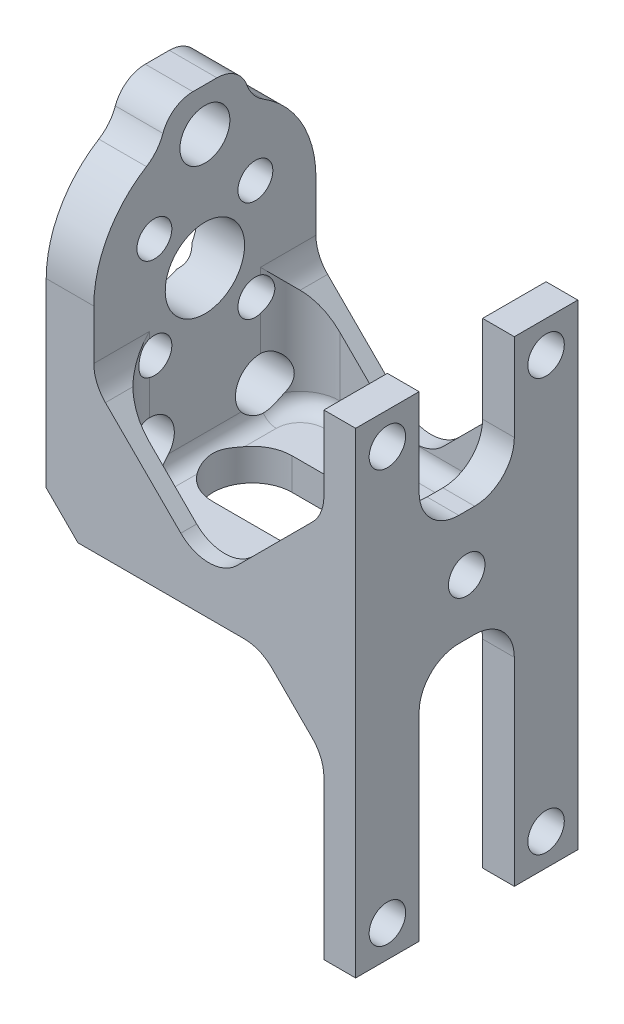
SolidWorks part; units mm, degrees
ref_plane "Front Plane" through (0, 0, 0) normal (0, 0, 1) x (1, 0, 0)
ref_plane "Top Plane" through (0, 0, 0) normal (0, 1, 0) x (1, 0, 0)
ref_plane "Right Plane" through (0, 0, 0) normal (1, 0, 0) x (0, 0, -1)
sketch "Sketch1" plane through (0, 0, 0) normal (0, 1, 0) x (1, 0, 0)
  line L0 (-7.25, 7) -> (7.25, -7) construction
  line L1 (-7.25, 7) -> (7.25, 7)
  line L2 (-7.25, 7) -> (-7.25, -7)
  line L3 (-7.25, -7) -> (7.25, -7)
  line L4 (7.25, 7) -> (7.25, -7)
  dimension "D2" = 14.5
  dimension "D1" = 14
extrude "base" add sketch "Sketch1" along normal blind 2
sketch "Sketch3" plane through (0, 0, 7) normal (0, 0, 1) x (1, 0, 0)
  line L0 (-7.25, 2) -> (7.25, 2) construction
  line L1 (-7.25, 0) -> (-10.25, 0)
  line L2 (-7.25, 0) -> (-7.25, 19)
  line L3 (-7.25, 19) -> (-10.25, 19)
  line L4 (-10.25, 0) -> (-10.25, 19)
  dimension "D1" = 3
  dimension "D2" = 17
extrude "motorFlange" add sketch "Sketch3" against normal up to surface (14 mm away) up to face at (0, 1, -7)
hole_wizard "CSK for M2 Flat Head Machine Screw1" positions "Sketch6" profile "Sketch7" countersink size "M2" standard "ANSI Metric"
sketch "Sketch6" plane through (-10.25, 0, 0) normal (-1, 0, 0) x (0, 0, 1)
  line L1 (-3.182, 15.182) -> (3.182, 15.182)
  line L2 (-3.182, 15.182) -> (-3.182, 8.818)
  line L3 (-3.182, 8.818) -> (3.182, 8.818)
  line L4 (3.182, 15.182) -> (3.182, 8.818)
  line L5 (0, 15.182) -> (0, 19)
  line L7 (-7, 19) -> (7, 19) construction
  line L8 (-3.182, 15.182) -> (3.182, 8.818) construction
  point P0 (-3.182, 15.182)
  point P2 (-3.182, 8.818)
  point P4 (3.182, 8.818)
  point P6 (3.182, 15.182)
  point P121 (0, 19)
  point P129 (0, 12)
  dimension "D3" = 7
  dimension "D1" = 9
sketch "Sketch7" plane through (-10.25, 15.182, -3.182) normal (0, 1, 0) x (0, 0, 1)
  line L0 (0, 0) -> (0, 5.8609)
  line L1 (0, 5.8609) -> (1.1, 5.2)
  line L2 (1.1, 5.2) -> (1.1, 1.1)
  line L3 (1.1, 1.1) -> (2.2, 0)
  line L5 (2.2, 0) -> (0, 0)
  line L6 (-1.1, 1.1) -> (-2.2, 0) construction
  line L10 (0, 5.8609) -> (-1.1, 5.2) construction
  line L11 (0, -6.35) -> (0, 107.95) construction
  dimension "Hole Dia." = 2.2
  dimension "Hole Depth" = 5.2
  dimension "Near C'Sink Dia." = 4.4
  dimension "Near C'Sink Angle" = 90
  dimension "Drill Angle" = 118
sketch "Sketch16" plane through (-10.25, 0, 0) normal (-1, 0, 0) x (0, 0, 1)
  line L0 (-3.182, 15.182) -> (3.182, 8.818) construction
  circle A0 centre (0, 12) radius 2.5
  dimension "D1" = 5
extrude "Cut-Extrude1" cut sketch "Sketch16" against normal blind 10
sketch "Sketch17" plane through (0, 19, 0) normal (0, 1, 0) x (1, 0, 0)
  line L0 (-7.25, 7) -> (-7.25, -7) construction
  line L1 (-10.25, 7) -> (-10.25, -7) construction
  line L2 (-7.25, -2.5) -> (-10.25, -2.5)
  line L3 (-7.25, -2.5) -> (-7.25, 2.5)
  line L4 (-7.25, 2.5) -> (-10.25, 2.5)
  line L5 (-10.25, -2.5) -> (-10.25, 2.5)
  point P8 (-7.25, 0)
  dimension "D1" = 5
extrude "Boss-Extrude5" add sketch "Sketch17" along normal blind 3
sketch "Sketch18" plane through (0, 2, 0) normal (0, 1, 0) x (1, 0, 0)
  line L0 (-7.25, 7) -> (-7.25, -7) construction
  line L1 (-7.25, 2.5) -> (-2.25, 2.5)
  line L2 (-7.25, 2.5) -> (-7.25, -2.5)
  line L3 (-7.25, -2.5) -> (-2.25, -2.5)
  line L4 (-2.25, 2.5) -> (-2.25, -2.5)
  point P6 (-7.25, 0)
  dimension "D1" = 5
  dimension "D2" = 5
extrude "Cut-Extrude2" [suppressed] cut sketch "Sketch18" against normal through all both and the other way through all
sketch "Sketch23" plane through (0, 0, 7) normal (0, 0, 1) x (1, 0, 0)
  line L0 (-10.25, 0) -> (10.554, -20.804) construction
  line L1 (-10.25, 0) -> (7.25, 0) construction
  dimension "D1" = 45
sketch "Sketch4" plane through (0, 0, 7) normal (0, 0, 1) x (1, 0, 0)
  line L1 (7.25, 0) -> (9.25, 0)
  line L2 (7.25, 0) -> (7.25, 7)
  line L3 (7.25, 7) -> (9.25, 7)
  line L4 (9.25, 0) -> (9.25, 7)
  line L5 (-7.25, 2) -> (7.25, 2) construction
  dimension "D1" = 2
  dimension "D2" = 5
extrude "Boss-Extrude3" add sketch "Sketch4" against normal up to surface (14 mm away) up to face at (-3.4167, 7, -7)
sketch "Sketch13" plane through (0, 7, 0) normal (0, 1, 0) x (1, 0, 0)
  line L0 (7.25, 7) -> (7.25, -7) construction
  line L1 (9.25, -7) -> (7.25, -7)
  line L2 (9.25, -7) -> (9.25, -3)
  line L3 (9.25, -3) -> (7.25, -3)
  line L4 (7.25, -7) -> (7.25, -3)
  dimension "D1" = 4
extrude "Boss-Extrude4" add sketch "Sketch13" along normal blind 8
mirror "Mirror5" about plane through (0, 0, 0) normal (0, 0, 1) of "Boss-Extrude4"
sketch "Sketch22" plane through (0, 0, 0) normal (0, -1, 0) x (1, 0, 0)
  line L1 (9.25, 7) -> (7.25, 7)
  line L2 (9.25, 7) -> (9.25, 3)
  line L3 (9.25, 3) -> (7.25, 3)
  line L4 (7.25, 7) -> (7.25, 3)
  line L5 (9.25, -7) -> (7.25, -7)
  line L6 (9.25, -7) -> (9.25, -3)
  line L7 (9.25, -3) -> (7.25, -3)
  line L8 (7.25, -7) -> (7.25, -3)
extrude "Boss-Extrude6" add sketch "Sketch22" along normal blind 15
sketch "Sketch26" plane through (0, 0, 7) normal (0, 0, 1) x (1, 0, 0)
  line L0 (-7.25, 9.25) -> (0, 2)
  line L1 (-7.25, 2) -> (-7.25, 19) construction
  line L2 (-7.25, 2) -> (7.25, 2) construction
  point P6 (7.25, 7.3453)
  dimension "D1" = 45
rib "Rib3" sketch "Sketch26" sketch "Sketch26" thickness 1 extrusion direction parallel to sketch draft on no parameters "D1"=1
sketch "Sketch27" plane through (0, 0, 7) normal (0, 0, 1) x (1, 0, 0)
  line L0 (0, 2) -> (7.25, 9.25)
  line L1 (7.25, 15) -> (7.25, 2) construction
  point P5 (0, 0)
rib "Rib4" sketch "Sketch27" sketch "Sketch27" thickness 1 extrusion direction parallel to sketch draft on no parameters "D1"=1
sketch "Sketch28" plane through (0, 0, 7) normal (0, 0, 1) x (1, 0, 0)
  line L0 (3.25, 0) -> (7.25, -4)
  line L1 (-10.25, 0) -> (7.25, 0) construction
  line L2 (7.25, -15) -> (7.25, 0) construction
  point P6 (0, 0)
  point P7 (3.1693, 0)
  dimension "D1" = 45
  dimension "D2" = 4
rib "Rib7" sketch "Sketch28" sketch "Sketch28" thickness 1 extrusion direction parallel to sketch draft on no parameters "D1"=1
mirror "Mirror7" about plane through (0, 0, 0) normal (0, 0, 1) of "Rib7", "Rib4", "Rib3"
fillet "Fillet5" radius 2.5 2 edges at (-8.75, 19, 2.5) (-8.75, 19, -2.5)
fillet "Fillet1" radius 7 2 edges at (-8.75, 19, -7) (-8.75, 19, 7)
fillet "Fillet6" radius 2 2 edges at (-8.75, 22, 2.5) (-8.75, 22, -2.5)
fillet "Fillet4" radius 2.5 2 edges at (8.25, 7, -3) (8.25, 7, 3)
fillet "Fillet8" radius 2.5 8 edges at (8.25, 0, -3) (8.25, 0, 3) (7.25, -4, -6.5) (3.25, 0, -6.5) (7.25, -4, 6.5) (3.25, 0, 6.5) (7.25, -2, 6) (7.25, -2, -6)
fillet "Fillet7" radius 1 6 edges at (7.25, 0, -2) (7.25, 0, 2) (3.4822, 0, -6) (3.4822, 0, 6) (6.5178, 0, 5.2678) (6.5178, 0, -5.2678)
fillet "Fillet13" radius 2.5 10 edges at (0, 2, 6.5) (-7.25, 9.25, 6.5) (-7.25, 5.625, 6) (-7.25, 5.625, -6) (7.25, 5.625, -6) (7.25, 5.625, 6) (7.25, 9.25, 6.5) (7.25, 9.25, -6.5) (-7.25, 9.25, -6.5) (0, 2, -6.5)
fillet "Fillet11" radius 1 10 edges at (7.25, 2, 0) (-7.25, 2, 0) (-2.375, 2, 6) (2.375, 2, 6) (-6.5178, 2, -5.2678) (6.5178, 2, 5.2678) (2.375, 2, -6) (-2.375, 2, -6) (6.5178, 2, -5.2678) (-6.5178, 2, 5.2678)
sketch "Sketch21" plane through (0, 2, 0) normal (0, 1, 0) x (1, 0, 0)
  line L1 (-7.25, -3.5) -> (-7.25, 3.5) construction
  circle A0 centre (-3.75, 0) radius 2.5
  point P5 (-7.25, 0)
  point P6 (-6.25, 0)
  dimension "D1" = 5
  dimension "D2" = 1
extrude "wireHole" [suppressed] cut sketch "Sketch21" against normal through all both and the other way through all
sketch "Sketch25" plane through (0, 2, 0) normal (0, 1, 0) x (1, 0, 0)
  line L0 (-4.25, 0) -> (0.75, 0) construction
  line L1 (-4.25, 2.5) -> (0.75, 2.5)
  line L2 (-4.25, -2.5) -> (0.75, -2.5)
  line L3 (-7.25, -3.5) -> (-7.25, 3.5) construction
  arc A0 (-4.25, 2.5) -> (-4.25, -2.5) centre (-4.25, 0) ccw
  arc A1 (0.75, -2.5) -> (0.75, 2.5) centre (0.75, 0) ccw
  point P3 (-1.75, 0)
  point P8 (-6.75, 0)
  point P11 (1.5738, -0.7462)
  point P12 (0, 0)
  point P13 (-7.25, 0)
  dimension "D2" = 5
  dimension "D3" = 2.5
  dimension "D1" = 0.5
extrude "wireSlot" cut sketch "Sketch25" against normal through all both and the other way through all
chamfer "Chamfer1" distance 2 angle 45 1 edges at (-10.25, 0, 0)
hole_wizard "Tapped Hole for M2.2x0.45 Helicoil1" positions "Sketch14" profile "Sketch15" tap size "M2.2x0.45" standard "Helicoil® Metric"
sketch "Sketch14" plane through (9.25, 0, 0) normal (1, 0, 0) x (0, 0, -1)
  line L0 (-5, 15) -> (-5, 13) construction
  line L1 (-7, 15) -> (-3, 15) construction
  line L3 (0, 7) -> (0, 0) construction
  line L6 (0.5, 0) -> (-0.5, 0) construction
  line L7 (-5, 13) -> (-7, 13) construction
  line L8 (-7, -15) -> (-7, 15) construction
  line L16 (-5, -15) -> (-5, -13) construction
  line L17 (-3, -15) -> (-7, -15) construction
  line L18 (0.5, 7) -> (-0.5, 7) construction
  point P0 (-5, 13)
  point P41 (0, 3.5)
  point P42 (5, 13)
  point P54 (-5, -13)
  point P60 (5, -13)
  point P66 (0, 0)
  point P67 (0, 0)
  point P68 (0, 3.75)
  point P69 (0, 7)
sketch "Sketch15" plane through (9.25, 13, 5) normal (0, 1, 0) x (0, 0, -1)
  line L0 (0, 0) -> (0, 6.691)
  line L1 (0, 6.691) -> (1.15, 6)
  line L2 (1.15, 6) -> (1.15, 0)
  line L5 (1.15, 0) -> (0, 0)
  line L10 (0, 6.691) -> (-1.15, 6) construction
  line L11 (0, -6.35) -> (0, 107.95) construction
  dimension "Tap Drill Dia." = 2.3
  dimension "Tap Drill Depth" = 6
  dimension "Drill Angle" = 118
cosmetic thread "Hole Thread7" parameters "D1"=2, "D2"=2.845
cosmetic thread "Hole Thread8" parameters "D1"=2.7, "D2"=2.845
cosmetic thread "Hole Thread9" parameters "D1"=2.7, "D2"=2.845
cosmetic thread "Hole Thread11" parameters "D1"=2.7, "D2"=2.845
cosmetic thread "Hole Thread12" parameters "D1"=2.7, "D2"=2.845
hole_wizard "Tapped Hole for M3x0.5 Helicoil1" positions "Sketch11" profile "Sketch12" tap size "M3x0.5" standard "Helicoil® Metric"
sketch "Sketch11" plane through (-10.25, 0, 0) normal (-1, 0, 0) x (0, 0, 1)
  line L0 (0, 0) -> (0, 19.2948) construction
  line L1 (-7, 0) -> (7, 0) construction
  line L2 (1.8358, 16.922) -> (0, 19.2948) construction
  line L4 (3.0416, 17.855) -> (0.6299, 15.9891) construction
  arc A0 (2.1803, 13.2233) -> (1.2233, 14.1803) centre (3.182, 15.182) ccw construction
  point P0 (3.5, 4)
  point P4 (0, 19.2948)
  point P16 (-3.5, 4)
  point P33 (1.8358, 16.922)
  dimension "D1" = 7
  dimension "D2" = 3
  dimension "D3" = 4
cosmetic thread "Hole Thread2" parameters "D1"=3.5, "D2"=3.716
cosmetic thread "Hole Thread3" parameters "D1"=3.5, "D2"=3.716
sketch "Sketch12" plane through (-10.25, 4, 3.5) normal (0, 1, 0) x (0, 0, 1)
  line L0 (0, 0) -> (0, 8.4464)
  line L1 (0, 8.4464) -> (1.575, 7.5)
  line L2 (1.575, 7.5) -> (1.575, 0)
  line L5 (1.575, 0) -> (0, 0)
  line L10 (0, 8.4464) -> (-1.575, 7.5) construction
  line L11 (0, -6.35) -> (0, 107.95) construction
  dimension "Tap Drill Dia." = 3.15
  dimension "Tap Drill Depth" = 7.5
  dimension "Drill Angle" = 118
cosmetic thread "Hole Thread10" parameters "D1"=3, "D2"=3.716
equation "\"motorDiameter\"= 14mm"
equation "\"baseThickness\"= 2mm"
equation "\"motorWallThickness\"= 3mm"
equation "\"boardWallThickness\"= \"baseThickness\""
equation "\"D1@base\" = \"baseThickness\""
equation "\"motorLength\"= 12.5mm"
equation "\"magnetHeight\"= 2mm"
equation "\"rotorClearance\"= 3mm"
equation "\"D1@Sketch3\"=\"motorWallThickness\""
equation "\"D2@Sketch3\"=\"motorDiameter\"+\"rotorClearance\""
equation "\"D1@Sketch4\"=\"boardWallThickness\""
equation "\"D1@Fillet1\"=\"motorDiameter\"/2"
equation "\"D3@Sketch6\"=\"motorDiameter\"/2"
equation "\"encoderClearance\"= 5mm"
equation "\"D2@Sketch4\"=\"motorDiameter\"/2+\"rotorClearance\"-\"encoderClearance\""
equation "\"cutterOD\"= 5mm"
equation "\"cutterSnubRadius\"= 1mm"
equation "\"D1@Fillet4\"= \"cutterOD\" / 2"
equation "\"D1@Sketch1\"=\"motorDiameter\""
equation "\"encoderClearance_vertical\"= 1mm"
equation "\"encoderHeight\"= 1mm"
equation "\"encoderWidth\"= 2mm"
equation "\"D2@Sketch1\"=\"motorLength\"+\"magnetHeight\"+\"encoderHeight\"+\"encoderClearance_vertical\"-\"boardWallThickness\""
equation "\"D1@Fillet5\"=\"cutterOD\"/2"
equation "\"D1@Fillet8\"=\"cutterOD\"/2"
equation "\"D1@Fillet11\"=\"cutterSnubRadius\""
equation "\"D1@Fillet7\"=\"cutterOD\"/2"
equation "\"D3@Sketch25\"=\"cutterOD\"/2"
equation "\"D1@Fillet7\"=\"cutterSnubRadius\"+0"
equation "\"D1@Fillet13\"=\"cutterOD\"/2"
